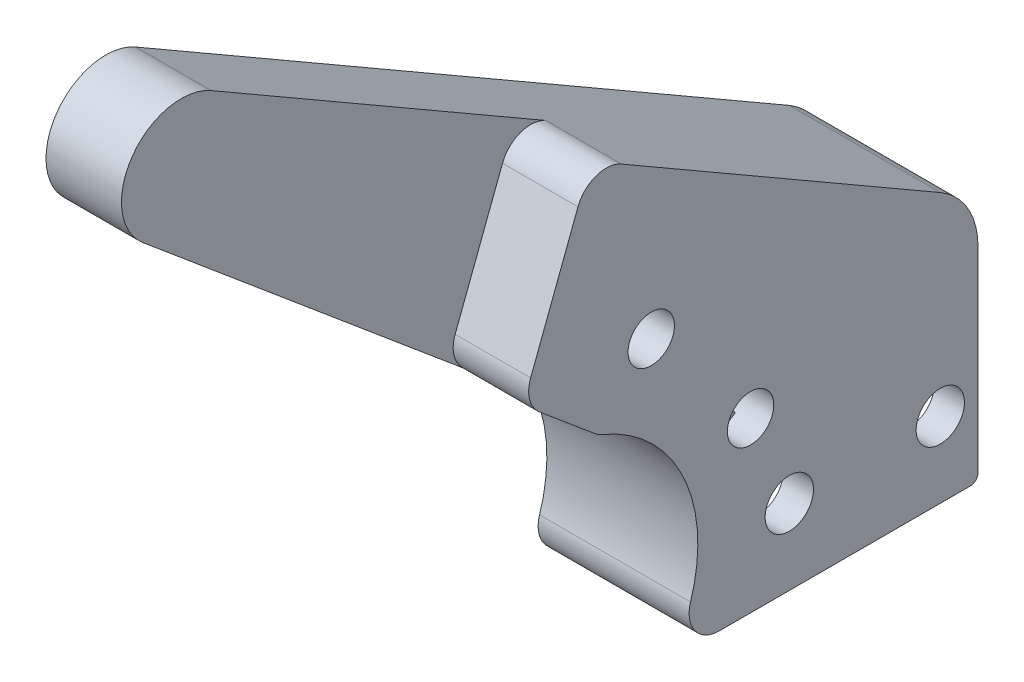
SolidWorks part; units mm, degrees
ref_plane "Front Plane" through (0, 0, 0) normal (0, 0, 1) x (1, 0, 0)
ref_plane "Top Plane" through (0, 0, 0) normal (0, 1, 0) x (1, 0, 0)
ref_plane "Right Plane" through (0, 0, 0) normal (1, 0, 0) x (0, 0, -1)
sketch "Sketch1" plane through (0, 0, 0) normal (1, 0, 0) x (0, 0, -1)
  line L0 (3.175, 6.35) -> (15.875, 6.35) construction
  line L1 (19.05, 0) -> (0, 0)
  line L2 (19.05, 0) -> (19.05, 17.145)
  line L4 (0, 0) -> (0, 17.145)
  line L6 (-2.6495, -67.6337) -> (6.077, -65.3632) construction
  line L7 (-17.4737, 7.2462) -> (1.7137, -66.4985) construction
  line L8 (-12.8878, 19.3613) -> (-44.8618, 46.1907)
  line L9 (15.875, 22.6443) -> (-39.1176, 54.3943)
  line L12 (0, 17.145) -> (19.05, 17.145) construction
  line L14 (0.635, 15.875) -> (13.6525, 15.875) construction
  line L15 (0, 12.7) -> (19.05, 12.7)
  line L17 (-6.736, 0) -> (0, 0)
  line L18 (-54.0982, 4.4381) -> (-21.5536, 58.9642) construction
  line L19 (-27.3828, 15.5899) -> (-12.5396, 54.6005) construction
  line L20 (-13.5422, 39.6283) -> (-21.1355, 19.6719)
  circle A0 centre (3.175, 6.35) radius 2.032
  circle A1 centre (15.875, 6.35) radius 2.032
  circle A2 centre (-17.4737, 7.2462) radius 12.7 construction
  arc A5 (-44.8618, 46.1907) -> (-39.1176, 54.3943) centre (-41.6309, 50.0412) cw
  arc A6 (15.875, 22.6443) -> (19.05, 17.145) centre (12.7, 17.145) cw
  arc A10 (-6.736, 0) -> (-12.8878, 19.3613) centre (-17.4737, 7.2462) ccw
  arc A11 (-12.5396, 54.6005) -> (-21.5536, 58.9642) centre (-17.2375, 56.3881) ccw construction
  point P8 (9.525, 6.35)
  point P9 (9.525, 0)
  point P10 (9.525, 6.35)
  point P11 (9.525, 0)
  point P18 (1.7137, -66.4985)
  dimension "D1" = 12.7
  dimension "D3" = 4.064
  dimension "D4" = 6.35
  dimension "D5" = 1.27
  dimension "D6" = 25.4
  dimension "D7" = 120
  dimension "D8" = 5.0265
  dimension "D12" = 63.5
  dimension "D11" = 6.35
  dimension "D13" = 12.7
  dimension "D14" = 12.954
  dimension "D18" = 7.2462
  dimension "D2" = 19.05
  dimension "D9" = 50
  dimension "D10" = 76.2
  dimension "D15" = 4.3873
  dimension "D16" = 10.795
  dimension "D17" = 75.416
  dimension "D19" = 20.6487
extrude "Boss-Extrude1" add sketch "Sketch1" along normal blind 2.54 contours A10 L17 L4 L12 A6 L9 L20 | L2 L12 L4 L1 A1 A0 | A10 L20 L9 A5 L8 region at (0, 6.35, -9.525) region at (0, 21.5758, 1.2184) region at (0, 41.3663, 29.5557)
extrude "Boss-Extrude2" add sketch "Sketch1<4>" against normal blind 7.62 contours A10 L17 L4 L12 A6 L9 L20 | A10 L20 L9 A5 L8 region at (0, 21.5758, 1.2184) region at (0, 41.3663, 29.5557)
sketch "Sketch1<4>" plane through (0, 0, 0) normal (1, 0, 0) x (0, 0, -1) same geometry as "Sketch1"
sketch "Sketch4" plane through (-7.62, 0, 0) normal (-1, 0, 0) x (0, 0, 1)
  line L6 (-19.05, 0) -> (6.736, 0)
  line L9 (-19.05, 17.145) -> (-19.05, 0)
  line L10 (39.1176, 54.3943) -> (-15.875, 22.6443)
  line L11 (12.8878, 19.3613) -> (44.8618, 46.1907)
  line L12 (-19.05, 0) -> (6.736, 0)
  line L15 (-19.05, 17.145) -> (-19.05, 0)
  line L16 (39.1176, 54.3943) -> (-15.875, 22.6443)
  line L17 (12.8878, 19.3613) -> (44.8618, 46.1907)
  circle A0 centre (-3.175, 6.35) radius 2.032 construction
  circle A1 centre (-15.875, 6.35) radius 2.032 construction
  circle A2 centre (-3.175, 6.35) radius 2.032
  circle A3 centre (-15.875, 6.35) radius 2.032
  arc A4 (12.8878, 19.3613) -> (6.736, 0) centre (17.4737, 7.2462) ccw
  arc A6 (-15.875, 22.6443) -> (-19.05, 17.145) centre (-12.7, 17.145) ccw
  arc A7 (44.8618, 46.1907) -> (39.1176, 54.3943) centre (41.6309, 50.0412) ccw
  arc A8 (12.8878, 19.3613) -> (6.736, 0) centre (17.4737, 7.2462) ccw
  arc A10 (-15.875, 22.6443) -> (-19.05, 17.145) centre (-12.7, 17.145) ccw
  arc A11 (44.8618, 46.1907) -> (39.1176, 54.3943) centre (41.6309, 50.0412) ccw
  dimension "D1" = 0
extrude "Boss-Extrude3" add sketch "Sketch4" along normal blind 2.54
sketch "Sketch5" plane through (2.54, 0, 0) normal (1, 0, 0) x (0, 0, -1)
  line L0 (-13.5422, 39.6283) -> (-21.1355, 19.6719) construction
  line L1 (-13.5422, 39.6283) -> (-21.1355, 19.6719)
  line L8 (-6.736, 0) -> (19.05, 0)
  line L11 (19.05, 0) -> (19.05, 17.145)
  line L12 (15.875, 22.6443) -> (-39.1176, 54.3943)
  line L13 (-44.8618, 46.1907) -> (-12.8878, 19.3613)
  line L14 (-6.736, 0) -> (19.05, 0)
  line L17 (19.05, 0) -> (19.05, 17.145)
  line L18 (15.875, 22.6443) -> (-39.1176, 54.3943)
  line L19 (-44.8618, 46.1907) -> (-12.8878, 19.3613)
  arc A4 (-6.736, 0) -> (-12.8878, 19.3613) centre (-17.4737, 7.2462) ccw
  arc A6 (19.05, 17.145) -> (15.875, 22.6443) centre (12.7, 17.145) ccw
  arc A7 (-39.1176, 54.3943) -> (-44.8618, 46.1907) centre (-41.6309, 50.0412) ccw
  arc A8 (-6.736, 0) -> (-12.8878, 19.3613) centre (-17.4737, 7.2462) ccw
  arc A10 (19.05, 17.145) -> (15.875, 22.6443) centre (12.7, 17.145) ccw
  arc A11 (-39.1176, 54.3943) -> (-44.8618, 46.1907) centre (-41.6309, 50.0412) ccw
  arc M11 (-12.8878, 19.3613) -> (-6.736, 0) centre (-17.4737, 7.2462) cw
  line M18 (15.875, 22.6443) -> (-39.1176, 54.3943)
  arc M19 (-39.1176, 54.3943) -> (-44.8618, 46.1907) centre (-41.6309, 50.0412) ccw
  line M20 (-44.8618, 46.1907) -> (-12.8878, 19.3613)
  dimension "D1" = 0
extrude "Cut-Extrude2" cut sketch "Sketch5" against normal blind 6.35 contours L1 M18 M19 M20 M11 region at (2.54, 41.3663, 29.5557)
fillet "Fillet1" radius 2.54 4 edges at (-3.81, 0, 6.736) (-0.635, 39.6283, 13.5422) (-3.81, 19.3613, 12.8878) (-0.635, 24.6823, 19.2291)
fillet "Fillet2" radius 0.635 4 edges at (-3.81, 0, 0) (-8.89, 0, -19.05) (1.27, 0, -19.05) (-3.81, 12.7, -19.05)
sketch "Sketch6" plane through (2.54, 0, 0) normal (1, 0, 0) x (0, 0, -1)
  line L0 (-0.9258, 7.678) -> (-14.9228, 24.3589) construction
  line L1 (-17.3312, 34.7371) -> (27535.6431, -32801.619) construction
  line L6 (-7.3737, 15.3576) -> (-3.6744, 18.4616) construction
  arc A0 (-5.1318, 3.3115) -> (-12.538, 19.2231) centre (-17.4737, 7.2462) ccw construction
  arc A1 (-5.1318, 3.3115) -> (-12.538, 19.2231) centre (-17.4737, 7.2462) ccw
  circle A2 centre (-0.0825, 14.181) radius 1.95
  circle A3 centre (-8.4388, 24.1395) radius 1.95
  dimension "D2" = 3.9
  dimension "D3" = 3.9
  dimension "D1" = 4.826
  dimension "D4" = 13
  dimension "D5" = 5.588
extrude "Cut-Extrude3" cut sketch "Sketch6" against normal through all contours A3 | A2 region at (2.54, 14.181, 0.0825) region at (2.54, 24.1395, 8.4388)
